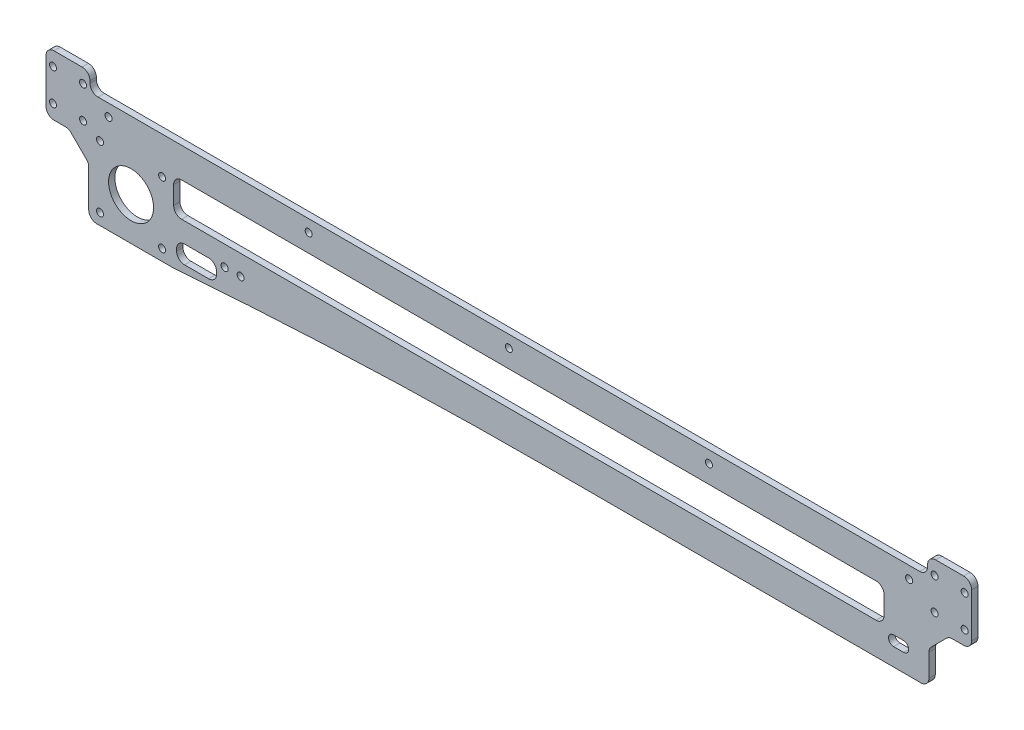
SolidWorks part; units mm, degrees
ref_plane "Front Plane" through (0, 0, 0) normal (0, 0, 1) x (1, 0, 0)
ref_plane "Top Plane" through (0, 0, 0) normal (0, 1, 0) x (1, 0, 0)
ref_plane "Right Plane" through (0, 0, 0) normal (1, 0, 0) x (0, 0, -1)
sketch "Sketch4" plane through (0, 0, 0) normal (0, 0, 1) x (1, 0, 0)
  line L0 (-220.25, 0) -> (220.25, 0) construction
  line L1 (0, 0) -> (0, -42) construction
  line L2 (-227.75, 8) -> (-212.75, 8) construction
  line L3 (-227.75, 8) -> (-227.75, -8) construction
  line L4 (-227.75, -8) -> (-212.75, -8) construction
  line L5 (-212.75, 8) -> (-212.75, -8) construction
  line L6 (-227.75, 8) -> (-212.75, -8) construction
  line L7 (-227.75, -8) -> (-212.75, 8) construction
  line L8 (212.75, 8) -> (227.75, 8) construction
  line L9 (212.75, 8) -> (212.75, -8) construction
  line L10 (212.75, -8) -> (227.75, -8) construction
  line L11 (227.75, 8) -> (227.75, -8) construction
  line L12 (212.75, 8) -> (227.75, -8) construction
  line L13 (212.75, -8) -> (227.75, 8) construction
  line L14 (-188.75, -28) -> (195.1367, -28) construction
  line L15 (-204.25, -43.5) -> (-173.25, -43.5) construction
  line L16 (-204.25, -43.5) -> (-204.25, -12.5) construction
  line L17 (-204.25, -12.5) -> (-173.25, -12.5) construction
  line L18 (-173.25, -43.5) -> (-173.25, -12.5) construction
  line L19 (-204.25, -43.5) -> (-173.25, -12.5) construction
  line L20 (-204.25, -12.5) -> (-173.25, -43.5) construction
  line L23 (-167.5, -9) -> (187.5, -9)
  line L24 (-167.5, -9) -> (-167.5, -26)
  line L25 (-167.5, -26) -> (187.5, -26)
  line L26 (187.5, -9) -> (187.5, -26)
  line L27 (-167.5, -9) -> (187.5, -26) construction
  line L28 (-167.5, -26) -> (187.5, -9) construction
  line L29 (-146, -45) -> (-166, -45)
  line L30 (-146, -45) -> (-146, -36)
  line L31 (-146, -36) -> (-166, -36)
  line L32 (-166, -45) -> (-166, -36)
  line L33 (-146, -45) -> (-166, -36) construction
  line L34 (-146, -36) -> (-166, -45) construction
  line L35 (-142, -36) -> (-134, -36) construction
  circle A0 centre (-227.75, 8) radius 1.75
  circle A1 centre (-212.75, 8) radius 1.75
  circle A2 centre (-227.75, -8) radius 1.75
  circle A3 centre (-212.75, -8) radius 1.75
  circle A4 centre (212.75, 8) radius 1.75
  circle A5 centre (227.75, 8) radius 1.75
  circle A6 centre (212.75, -8) radius 1.75
  circle A7 centre (227.75, -8) radius 1.75
  circle A8 centre (0, 0) radius 1.75
  circle A9 centre (100, 0) radius 1.75
  circle A10 centre (200, 0) radius 1.75
  circle A11 centre (-200, 0) radius 1.75
  circle A12 centre (-100, 0) radius 1.75
  circle A14 centre (-188.75, -28) radius 11.25
  circle A17 centre (-204.25, -12.5) radius 1.75
  circle A18 centre (-173.25, -12.5) radius 1.75
  circle A19 centre (-204.25, -43.5) radius 1.75
  circle A20 centre (-173.25, -43.5) radius 1.75
  circle A21 centre (-142, -36) radius 1.75
  circle A22 centre (-134, -36) radius 1.75
  point P4 (0, 0)
  point P41 (10, -17.5)
  point P44 (-156, -40.5)
  point P56 (-138, -36)
  dimension "D4" = 3.5
  dimension "D6" = 100
  dimension "D7" = 22.5
  dimension "D8" = 28
  dimension "D9" = 31.5
  dimension "D10" = 31
  dimension "D22" = 42
  dimension "D1" = 440.5
  dimension "D2" = 15
  dimension "D3" = 16
  dimension "D11" = 355
  dimension "D12" = 10
  dimension "D13" = 9
  dimension "D14" = 17
  dimension "D15" = 20
  dimension "D16" = 32.75
  dimension "D17" = 9
  dimension "D18" = 12.5
  dimension "D19" = 8
  dimension "D20" = 4.5
  dimension "D21" = 18
  dimension "D5" = 3
sketch "Sketch5" plane through (0, 0, 0) normal (0, 0, 1) x (1, 0, 0)
  line L0 (-166, -45) -> (-166, -36) construction
  line L1 (-146, -36) -> (-166, -36) construction
  line L2 (-146, -45) -> (-146, -36) construction
  line L3 (-146, -45) -> (-166, -45) construction
  line L4 (187.5, -9) -> (187.5, -26) construction
  line L5 (-167.5, -26) -> (187.5, -26) construction
  line L6 (-167.5, -9) -> (187.5, -9) construction
  line L7 (-167.5, -9) -> (-167.5, -26) construction
  line L8 (-166, -45) -> (-166, -36)
  line L9 (-146, -36) -> (-166, -36)
  line L10 (-146, -45) -> (-146, -36)
  line L11 (-146, -45) -> (-166, -45)
  line L12 (187.5, -9) -> (187.5, -26)
  line L13 (-167.5, -26) -> (187.5, -26)
  line L14 (-167.5, -9) -> (187.5, -9)
  line L15 (-167.5, -9) -> (-167.5, -26)
  line L16 (-209.9, -15) -> (-209.9, -49.15)
  line L17 (-231.25, -15) -> (-209.9, -15)
  line L18 (-231.25, -15) -> (-231.25, 15)
  line L19 (-231.25, 15) -> (-209.25, 15)
  line L20 (-209.25, -15) -> (-209.25, 6) construction
  line L21 (-231.25, -15) -> (-209.25, 15) construction
  line L22 (-231.25, 15) -> (-209.25, -15) construction
  line L23 (-209.9, -49.15) -> (-167.6, -49.15)
  line L24 (0, 0) -> (0, -42) construction
  line L25 (0, 0) -> (0, -42) construction
  line L26 (231.25, -15) -> (209.9, -15)
  line L27 (231.25, -15) -> (231.25, 15)
  line L28 (231.25, 15) -> (209.25, 15)
  line L29 (209.25, -15) -> (209.25, 6) construction
  line L30 (-209.25, 6) -> (209.25, 6)
  line L31 (209.9, -15) -> (209.9, -41.9092)
  line L32 (-209.9, -15) -> (-209.25, -15) construction
  line L33 (-209.25, 6) -> (-209.25, 15)
  line L34 (209.9, -15) -> (209.25, -15) construction
  line L35 (209.25, 6) -> (209.25, 15)
  line L36 (209.9, -41.9092) -> (21.15, -41.9092)
  line L37 (209.9, -41.9092) -> (209.9, -49.15) construction
  line L38 (197.25, -30.5) -> (192.25, -30.5) construction
  line L39 (197.25, -33.05) -> (192.25, -33.05)
  line L40 (197.25, -27.95) -> (192.25, -27.95)
  circle A0 centre (-134, -36) radius 1.75 construction
  circle A1 centre (-142, -36) radius 1.75 construction
  circle A2 centre (-173.25, -43.5) radius 1.75 construction
  circle A3 centre (-204.25, -43.5) radius 1.75 construction
  circle A4 centre (-188.75, -28) radius 11.25 construction
  circle A5 centre (-173.25, -12.5) radius 1.75 construction
  circle A6 centre (-204.25, -12.5) radius 1.75 construction
  circle A7 centre (212.75, -8) radius 1.75 construction
  circle A8 centre (227.75, -8) radius 1.75 construction
  circle A9 centre (227.75, 8) radius 1.75 construction
  circle A10 centre (212.75, 8) radius 1.75 construction
  circle A11 centre (200, 0) radius 1.75 construction
  circle A12 centre (100, 0) radius 1.75 construction
  circle A13 centre (0, 0) radius 1.75 construction
  circle A14 centre (-100, 0) radius 1.75 construction
  circle A15 centre (-200, 0) radius 1.75 construction
  circle A16 centre (-212.75, -8) radius 1.75 construction
  circle A17 centre (-212.75, 8) radius 1.75 construction
  circle A18 centre (-227.75, -8) radius 1.75 construction
  circle A19 centre (-227.75, 8) radius 1.75 construction
  circle A20 centre (-134, -36) radius 1.75
  circle A21 centre (-142, -36) radius 1.75
  circle A22 centre (-173.25, -43.5) radius 1.75
  circle A23 centre (-204.25, -43.5) radius 1.75
  circle A24 centre (-188.75, -28) radius 11.25
  circle A25 centre (-173.25, -12.5) radius 1.75
  circle A26 centre (-204.25, -12.5) radius 1.75
  circle A27 centre (212.75, -8) radius 1.75
  circle A28 centre (227.75, -8) radius 1.75
  circle A29 centre (227.75, 8) radius 1.75
  circle A30 centre (212.75, 8) radius 1.75
  circle A31 centre (200, 0) radius 1.75
  circle A32 centre (100, 0) radius 1.75
  circle A33 centre (0, 0) radius 1.75
  circle A34 centre (-100, 0) radius 1.75
  circle A35 centre (-200, 0) radius 1.75
  circle A36 centre (-212.75, -8) radius 1.75
  circle A37 centre (-212.75, 8) radius 1.75
  circle A38 centre (-227.75, -8) radius 1.75
  circle A39 centre (-227.75, 8) radius 1.75
  arc A40 (-167.6, -49.15) -> (21.15, -41.9092) centre (21.15, -2505.6617) cw
  arc A41 (21.15, -41.9092) -> (209.9, -49.15) centre (21.15, -2505.6617) cw construction
  arc A42 (197.25, -33.05) -> (197.25, -27.95) centre (197.25, -30.5) ccw
  arc A43 (192.25, -27.95) -> (192.25, -33.05) centre (192.25, -30.5) ccw
  circle A45 centre (197.25, -30.5) radius 8.75 construction
  point P0 (10, -17.5)
  point P2 (220.25, 0)
  point P4 (-220.25, 0)
  point P74 (-220.25, 0)
  point P97 (194.75, -30.5)
  dimension "D8" = 5.1
  dimension "D11" = 17.5
  dimension "D1" = 22
  dimension "D2" = 30
  dimension "D3" = 21.15
  dimension "D4" = 21.15
  dimension "D5" = 6
  dimension "D6" = 42.3
  dimension "D7" = 42
  dimension "D9" = 2.5
  dimension "D10" = 5
  dimension "D12" = 23
base flange "Base-Flange1" sketch "Sketch5" thickness 3.175 reverse thickness direction no parameters "D1"=3
fillet "Fillet1" radius 4 13 edges at (-167.6, -49.15, -1.5875) (-209.9, -49.15, -1.5875) (209.25, 6, -1.5875) (-209.25, 6, -1.5875) (187.5, -26, -1.5875) (187.5, -9, -1.5875) (-167.5, -26, -1.5875) (-167.5, -9, -1.5875) (-146, -36, -1.5875) (-146, -45, -1.5875) (-166, -45, -1.5875) (-166, -36, -1.5875) (209.9, -41.9092, -1.5875)
chamfer "Chamfer1" distance 10 angle 45 2 edges at (209.9, -15, -1.5875) (-209.9, -15, -1.5875)
fillet "Fillet2" radius 4 10 edges at (-231.25, -15, -1.5875) (-231.25, 15, -1.5875) (-209.25, 15, -1.5875) (-209.9, -25, -1.5875) (-219.9, -15, -1.5875) (209.9, -25, -1.5875) (219.9, -15, -1.5875) (231.25, -15, -1.5875) (231.25, 15, -1.5875) (209.25, 15, -1.5875)
sketch "Sketch6" plane through (0, 0, 0) normal (0, 0, 1) x (1, 0, 0)
  line L0 (-142, -36) -> (-134, -36) construction
sketch "Bend-Lines1" [suppressed] plane through (0, 0, 0) normal (0, 1, 0) x (1, 0, 0)
sketch "Bounding-Box1" [suppressed] plane through (0, 0, 0) normal (0, 1, 0) x (1, 0, 0)
sheet metal parameters "Sheet-Metal1" thickness 3.175 parameters "D1"=3
flat pattern "Flat-Pattern1" [suppressed]
sketch "Bend-Lines2" plane through (0, 0, 0) normal (0, 1, 0) x (1, 0, 0)
sketch3d "Bounding-Box2" [suppressed]
  line L0 (-252.4, 2456.5117, 0) -> (210.1, 2456.5117, 0) construction
  line L1 (-252.4, 2520.6617, 0) -> (210.1, 2520.6617, 0) construction
  line L2 (-252.4, 2456.5117, 0) -> (-252.4, 2520.6617, 0) construction
  line L3 (210.1, 2456.5117, 0) -> (210.1, 2520.6617, 0) construction
equation "\"D4@Sketch5\"=\"D3@Sketch5\""
equation "\"D6@Sketch5\"=\"D3@Sketch5\"*2"
